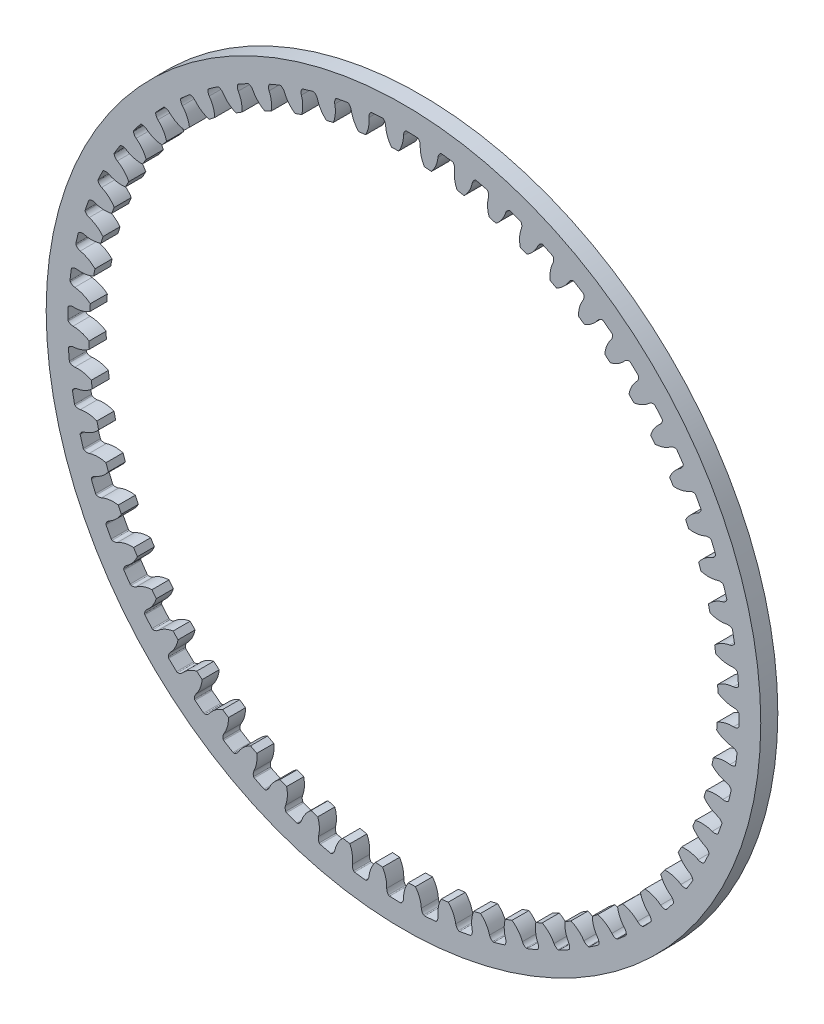
SolidWorks part; units mm, degrees
ref_plane "Ebene vorne (XY)" through (0, 0, 0) normal (0, 0, 1) x (1, 0, 0)
ref_plane "Ebene oben  (XZ)" through (0, 0, 0) normal (0, 1, 0) x (1, 0, 0)
ref_plane "Ebene rechts  (YZ)" through (0, 0, 0) normal (1, 0, 0) x (0, 0, -1)
ref_axis "x-Achse" through (-80.685, 0, 0) along (1, 0, 0)
ref_axis "y-Achse" through (0, 80.685, 0) along (0, -1, 0)
ref_axis "z-Achse" through (0, 0, -0.175) along (0, 0, 1)
sketch "Sketch1" plane through (0, 0, 0) normal (0, 0, 1) x (1, 0, 0)
  line L0 (1.8448, 73.3268) -> (0, 0) construction
  line L1 (0, 0) -> (-13.4411, 72.108) construction
  circle A0 centre (0, 0) radius 73.35 construction
  line B0 (-7.0932, 67.4873) -> (-7.2031, 68.5325)
  line B1 (1.7331, 68.8882) -> (1.8448, 73.3268)
  line B2 (-3.7236, 68.8093) -> (-3.6691, 67.8011)
  line B3 (-10.7361, 67.0462) -> (-10.8958, 68.0431)
  line B4 (-12.6274, 67.7432) -> (-13.4411, 72.108)
  line B5 (0, 68.91) -> (0, 67.859)
  line B6 (-2.4613, 64.5035) -> (-0.9996, 64.543)
  line B7 (-9.1903, 63.8928) -> (-7.7407, 64.0849)
  arc B8 (-0.9996, 64.543) -> (0, 67.859) centre (-6, 67.859) ccw
  arc B9 (-3.6691, 67.8011) -> (-2.4613, 64.5035) centre (2.3221, 68.1254) ccw
  arc B10 (1.7331, 68.8882) -> (0, 68.91) centre (0, 0) ccw
  arc B11 (-7.7407, 64.0849) -> (-7.0932, 67.4873) centre (-13.0603, 66.8601) ccw
  arc B12 (-10.7361, 67.0462) -> (-9.1903, 63.8928) centre (-4.8116, 67.9949) ccw
  arc B13 (-10.8958, 68.0431) -> (-12.6274, 67.7432) centre (0, 0) ccw
  arc B14 (-3.7236, 68.8093) -> (-7.2031, 68.5325) centre (0, 0) ccw
  arc B15 (1.8448, 73.3268) -> (-13.4411, 72.108) centre (0, 0) ccw
sketch_block_instance "Block1-1"
sketch_block "Block1"
extrude "Boss-Extrude1" add sketch "Sketch1" along normal blind 3.5
ref_axis "Axis1" through (0, 0, -0.175) along (0, 0, 1)
chamfer "Chamfer1" distance 0.5 angle 45 4 edges at (0, 68.91, 1.75) (-10.8958, 68.0431, 1.75) (-3.7236, 68.8093, 1.75) (-7.2031, 68.5325, 1.75)
fillet "Fillet2" radius 1.4 4 edges at (0, 68.41, 1.75) (-3.6966, 68.3101, 1.75) (-7.1508, 68.0352, 1.75) (-10.8167, 67.5494, 1.75)
fillet "Fillet3" radius 0.3 4 edges at (-11.3874, 67.9626, 1.75) (0.4982, 68.9082, 1.75) (-4.221, 68.7806, 1.75) (-6.7074, 68.5828, 1.75)
fillet "Fillet4" [suppressed] radius 1
pattern_circular "CirPattern1" count 30 over 360 about axis through (0, 0, -0.175) along (0, 0, 1) of "Fillet3", "Boss-Extrude1", "Chamfer1", "Fillet2", "Fillet4" reverse direction yes
